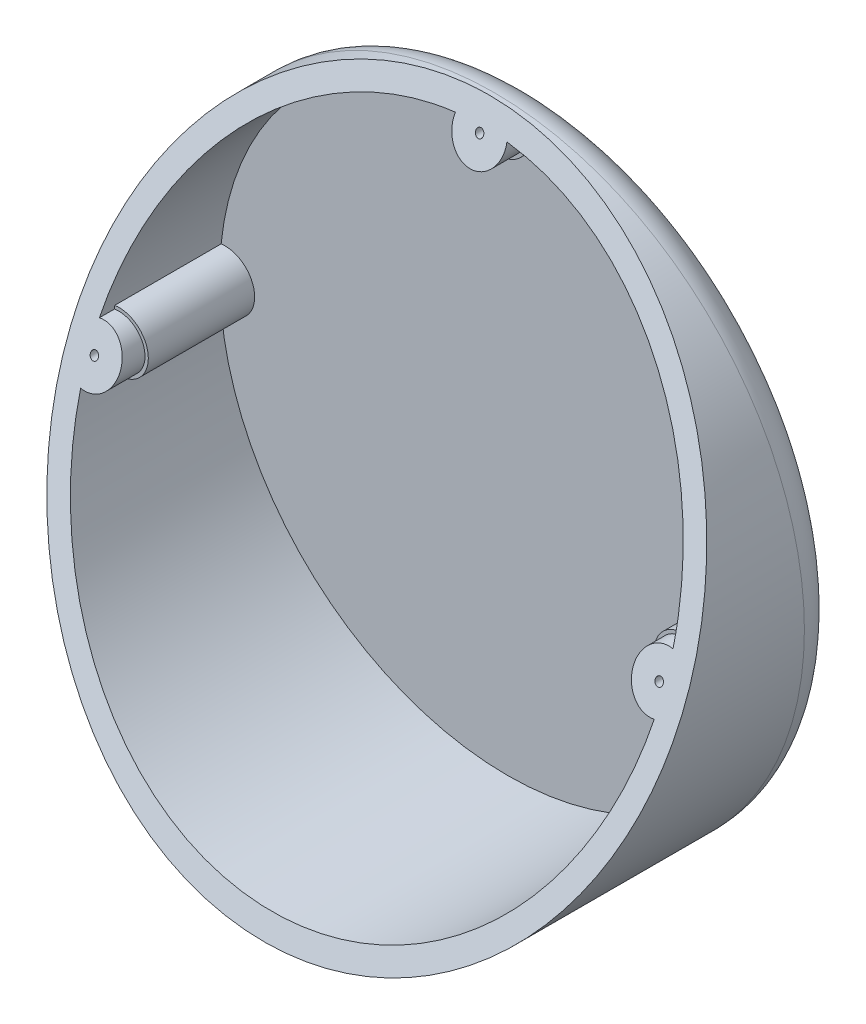
SolidWorks part; units mm, degrees
ref_plane "前视基准面" through (0, 0, 0) normal (0, 0, 1) x (1, 0, 0)
ref_plane "上视基准面" through (0, 0, 0) normal (0, 1, 0) x (1, 0, 0)
ref_plane "右视基准面" through (0, 0, 0) normal (1, 0, 0) x (0, 0, -1)
sketch "草图1" plane through (0, 0, 0) normal (0, 0, 1) x (1, 0, 0)
  circle A0 centre (0, 0) radius 70
  dimension "D1" = 140
extrude "凸台-拉伸1" add sketch "草图1" along normal blind 60
sketch "草图2" plane through (0, 0, 0) normal (1, 0, 0) x (0, 0, -1)
  line L0 (-60, -70) -> (-60, 70)
  line L1 (-60, 70) -> (-9.0442, 70)
  line L2 (0, 70) -> (-60, 70) construction
  line L3 (-9.0442, 70) -> (-60, -70)
  dimension "D1" = 20
extrude "切除-拉伸1" cut sketch "草图2" against normal through all and the other way through all
hole_wizard "打孔尺寸(%根据)内六角圆柱头螺钉的类型1" positions "草图5" profile "草图4" counterbore size "M1.6" standard "GB" end condition through all
sketch "草图5" plane through (0, 0, 0) normal (0, 0, -1) x (-1, 0, 0)
  line L0 (0, 0) -> (0, 72.8729) construction
  circle A0 centre (0, 0) radius 63.75 construction
  point P0 (0, 63.75)
  dimension "D1" = 127.5
sketch "草图4" plane through (0, 63.75, 0) normal (1, 0, 0) x (0, 1, 0)
  line L0 (0, 0) -> (0, 60)
  line L1 (0, 60) -> (0.9, 60)
  line L3 (0.9, 60) -> (0.9, 1.8)
  line L4 (0.9, 1.8) -> (1.65, 1.8)
  line L5 (1.65, 1.8) -> (1.65, 0)
  line L7 (1.65, 0) -> (0, 0)
  line L11 (0, -6.35) -> (0, 107.95) construction
  dimension "通孔孔直径" = 1.8
  dimension "通孔孔深度" = 60
  dimension "柱形沉头孔直径" = 3.3
  dimension "柱形沉头孔深度" = 1.8
hole_wizard "打孔尺寸(%根据)内六角圆柱头螺钉的类型2" positions "草图8" profile "草图7" counterbore size "M1.6" standard "GB" end condition through all
sketch "草图8" plane through (0, 0, 0) normal (0, 0, -1) x (-1, 0, 0)
  line L0 (-75.9714, 0) -> (87.4475, 0) construction
  circle A0 centre (0, 0) radius 63.75 construction
  point P0 (-63.75, 0)
  point P2 (63.75, 0)
  dimension "D1" = 127.5
sketch "草图7" plane through (63.75, 0, 0) normal (1, 0, 0) x (0, 1, 0)
  line L0 (0, 0) -> (0, 60)
  line L1 (0, 60) -> (0.9, 60)
  line L3 (0.9, 60) -> (0.9, 24)
  line L4 (0.9, 24) -> (1.65, 24)
  line L5 (1.65, 24) -> (1.65, 0)
  line L7 (1.65, 0) -> (0, 0)
  line L11 (0, -6.35) -> (0, 107.95) construction
  dimension "通孔孔直径" = 1.8
  dimension "通孔孔深度" = 60
  dimension "柱形沉头孔直径" = 3.3
  dimension "柱形沉头孔深度" = 24
shell "抽壳1" thickness 5 removed face at (63.75, 0.9, 34.1945)
fillet "圆角2" radius 8 1 edges at (70, 0, 0)
